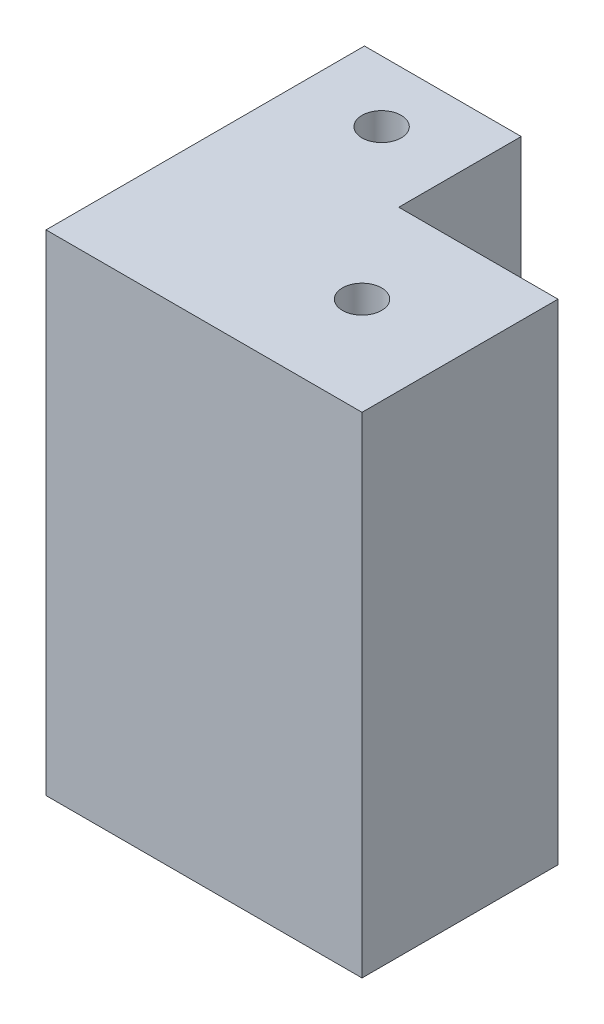
SolidWorks part; units mm, degrees
ref_plane "Front Plane" through (0, 0, 0) normal (0, 0, 1) x (1, 0, 0)
ref_plane "Top Plane" through (0, 0, 0) normal (0, 1, 0) x (1, 0, 0)
ref_plane "Right Plane" through (0, 0, 0) normal (1, 0, 0) x (0, 0, -1)
sketch "Sketch1" plane through (0, 0, 0) normal (0, 1, 0) x (1, 0, 0)
  line L0 (0, 0) -> (0, 25)
  line L1 (0, 25) -> (-32, 25)
  line L2 (-32, 25) -> (-32, -40)
  line L3 (-32, -40) -> (32.5, -40)
  line L4 (32.5, -40) -> (32.5, 0)
  line L5 (32.5, 0) -> (0, 0)
  line L6 (-32, 0) -> (0, 0) construction
  line L7 (0, -40) -> (0, 0) construction
  line L8 (0, 25) -> (-32, 0) construction
  line L9 (25, 25) -> (25, 0) construction
  line L10 (0, 25) -> (25, 25) construction
  line L11 (25, 0) -> (0, -40) construction
  circle A0 centre (-16, 12.5) radius 4
  circle A1 centre (12.5, -20) radius 4
  circle A2 centre (-16, 12.5) radius 11 construction
  circle A3 centre (-16, 12.5) radius 6 construction
  circle A4 centre (12.5, -20) radius 6.75 construction
  circle A5 centre (12.5, -20) radius 16 construction
  point P17 (0, 0)
  dimension "D4" = 8
  dimension "D5" = 22
  dimension "D6" = 12
  dimension "D7" = 13.5
  dimension "D8" = 32
  dimension "D1" = 25
  dimension "D2" = 25
  dimension "D3" = 40
  dimension "D9" = 41
  dimension "D10" = 20
extrude "Boss-Extrude1" add sketch "Sketch1" along normal blind 100
ref_plane "Plane1" through (0, 0, 0) normal (0, -1, 0) x (-1, 0, 0)
sketch "Sketch4" plane through (0, 0, 0) normal (0, -1, 0) x (-1, 0, 0)
  line L7 (0, -40) -> (0, 0) construction
  line L12 (-25, 0) -> (0, -40) construction
  line L13 (0, 25) -> (-25, 25) construction
  line L14 (-25, 25) -> (-25, 0) construction
  line L15 (0, 25) -> (32, 0) construction
  line L16 (32, 0) -> (0, 0) construction
  line L17 (-32.5, 0) -> (0, 0) construction
  line L18 (-32.5, -40) -> (-32.5, 0) construction
  line L19 (32, -40) -> (-32.5, -40) construction
  line L20 (32, 25) -> (32, -40) construction
  line L21 (0, 25) -> (32, 25) construction
  line L22 (0, 0) -> (0, 25) construction
  circle A6 centre (-12.5, -20) radius 16 construction
  circle A7 centre (-12.5, -20) radius 6.75 construction
  circle A8 centre (16, 12.5) radius 6 construction
  circle A9 centre (16, 12.5) radius 11 construction
  circle A10 centre (-12.5, -20) radius 4
  circle A11 centre (16, 12.5) radius 4
  point P20 (-12.5, -20)
  dimension "D3" = 32
  dimension "D4" = 40
  dimension "D5" = 8
  dimension "D6" = 13.5
  dimension "D7" = 32
  dimension "D8" = 8
  dimension "D9" = 12
  dimension "D10" = 22
  dimension "D1" = 25
  dimension "D2" = 25
hole_wizard "CBORE for M5 Hex Head Bolt1" positions "Sketch4" profile "Sketch7" counterbore size "M5" standard "ANSI Metric"
sketch "Sketch7" plane through (12.5, 0, 20) normal (1, 0, 0) x (0, 0, -1)
  line L0 (0, 0) -> (0, 30)
  line L1 (0, 30) -> (4, 30)
  line L2 (4, 30) -> (4, 23.85)
  line L3 (4, 23.85) -> (6.75, 23.85)
  line L4 (6.75, 23.85) -> (6.75, 0)
  line L5 (6.75, 0) -> (0, 0)
  line L10 (0, 30) -> (-4, 30) construction
  line L11 (0, -6.35) -> (0, 107.95) construction
  dimension "Hole Dia." = 8
  dimension "Hole Depth" = 30
  dimension "C'Bore Dia." = 13.5
  dimension "C'Bore Depth" = 23.85
  dimension "Drill Angle" = 180
sketch "Sketch8" plane through (0, 0, 0) normal (0, -1, 0) x (-1, 0, 0)
  point P0 (-12.5, -20)
hole_wizard "CBORE for M5 Hex Head Bolt2" positions "Sketch8" profile "Sketch9" counterbore size "M5" standard "ANSI Metric"
sketch "Sketch9" plane through (12.5, 0, 20) normal (1, 0, 0) x (0, 0, -1)
  line L0 (0, 0) -> (0, 23.85)
  line L1 (0, 23.85) -> (6.75, 23.85)
  line L2 (6.75, 23.85) -> (6.75, 5)
  line L3 (6.75, 5) -> (16, 5)
  line L4 (16, 5) -> (16, 0)
  line L5 (16, 0) -> (0, 0)
  line L10 (0, 23.85) -> (-6.75, 23.85) construction
  line L11 (0, -6.35) -> (0, 107.95) construction
  dimension "Hole Dia." = 13.5
  dimension "Hole Depth" = 23.85
  dimension "C'Bore Dia." = 32
  dimension "C'Bore Depth" = 5
  dimension "Drill Angle" = 180
sketch "Sketch10" plane through (0, 0, 0) normal (0, -1, 0) x (-1, 0, 0)
  point P0 (16, 12.5)
hole_wizard "CBORE for M5 Hex Head Bolt3" positions "Sketch10" profile "Sketch11" counterbore size "M5" standard "ANSI Metric"
sketch "Sketch11" plane through (-16, 0, -12.5) normal (1, 0, 0) x (0, 0, -1)
  line L0 (0, 0) -> (0, 10)
  line L1 (0, 10) -> (5.1, 10)
  line L2 (5.1, 10) -> (5.1, 3.5)
  line L3 (5.1, 3.5) -> (11, 3.5)
  line L4 (11, 3.5) -> (11, 0)
  line L5 (11, 0) -> (0, 0)
  line L10 (0, 10) -> (-5.1, 10) construction
  line L11 (0, -6.35) -> (0, 107.95) construction
  dimension "Hole Dia." = 10.2
  dimension "Hole Depth" = 10
  dimension "C'Bore Dia." = 22
  dimension "C'Bore Depth" = 3.5
  dimension "Drill Angle" = 180
